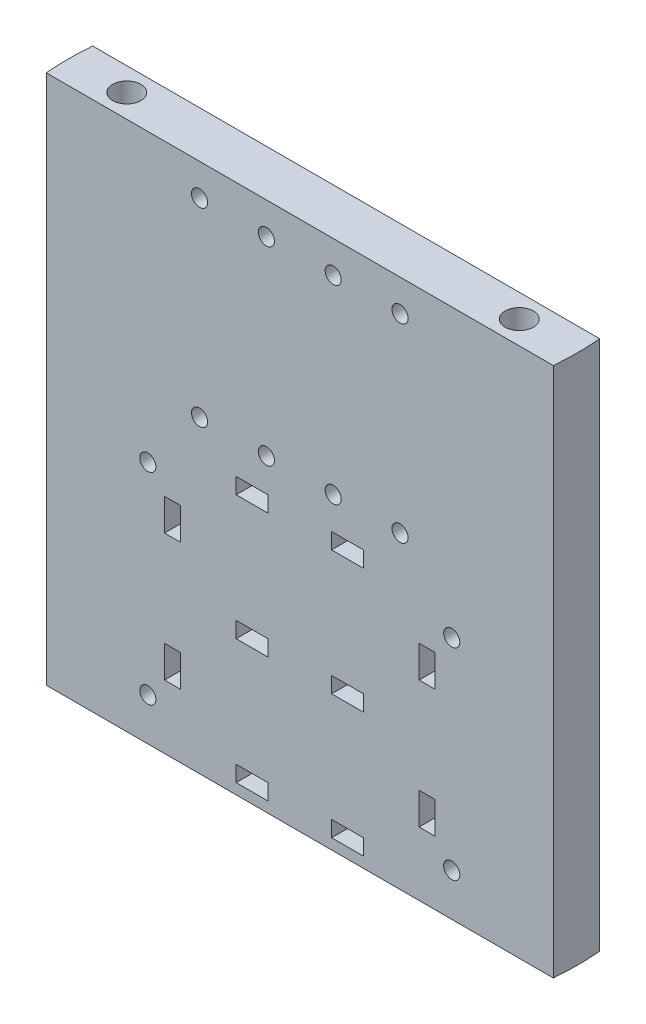
SolidWorks part; units mm, degrees
ref_plane "Front Plane" through (0, 0, 0) normal (0, 0, 1) x (1, 0, 0)
ref_plane "Top Plane" through (0, 0, 0) normal (0, 1, 0) x (1, 0, 0)
ref_plane "Right Plane" through (0, 0, 0) normal (1, 0, 0) x (0, 0, -1)
sketch "Sketch1" plane through (0, 0, 0) normal (0, 1, 0) x (1, 0, 0)
  line L0 (-60.706, 5.5591) -> (60.706, 5.5591)
  line L1 (-60.706, -5.5591) -> (60.706, -5.5591)
  arc A0 (60.706, -5.5591) -> (60.706, 5.5591) centre (0, 0) ccw
  arc A1 (-60.706, 5.5591) -> (-60.706, -5.5591) centre (0, 0) ccw
  point P1 (0, 5.5591)
  dimension "D1" = 121.92
  dimension "D4" = 60.96
  dimension "D2" = 121.412
  dimension "D3" = 121.412
  dimension "D5" = 5.5591
extrude "Boss-Extrude1" add sketch "Sketch1" along normal blind 127 contours L1 | L1 | L1 A0 L0 A1 region at (0, 0, 0)
sketch "Sketch2" plane through (0, 0, 0) normal (0, 1, 0) x (1, 0, 0)
  circle A0 centre (0, 0) radius 61.595
  dimension "D1" = 123.19
sketch "Sketch3" plane through (0, 0, 0) normal (0, 1, 0) x (1, 0, 0)
  circle A0 centre (0, 0) radius 63.5
  dimension "D1" = 127
ref_plane "Raft Top" through (0, 0, 9.9465) normal (0, 0, -1) x (-1, 0, 0)
sketch "Sketch10" plane through (0, 0, -5.5591) normal (0, 0, -1) x (-1, 0, 0)
  line L0 (-32.385, 2.54) -> (-32.385, 66.04)
  line L5 (-32.385, 66.04) -> (32.385, 66.04)
  line L10 (32.385, 66.04) -> (32.385, 2.54)
  line L11 (32.385, 2.54) -> (-32.385, 2.54)
  line L16 (60.706, 127) -> (60.706, 0) construction
  line L17 (61.595, 0) -> (-61.595, 0) construction
  line L18 (-60.706, 127) -> (-60.706, 0) construction
  dimension "D1" = 28.321
  dimension "D2" = 2.54
  dimension "D3" = 28.321
  dimension "D4" = 63.5
  dimension "D5" = 64.77
sketch "Sketch13" plane through (0, 127, 0) normal (0, 1, 0) x (1, 0, 0)
  line L2 (60.706, 5.5591) -> (-60.706, 5.5591)
  line L3 (-60.706, -5.5591) -> (60.706, -5.5591)
  line L4 (60.706, 5.5591) -> (-60.706, 5.5591)
  line L5 (-60.706, -5.5591) -> (60.706, -5.5591)
  line L6 (-46.99, 5.5591) -> (-46.99, -5.5591) construction
  line L7 (0, -55) -> (0, 55) construction
  line L8 (-32.385, 5.5591) -> (32.385, 5.5591) construction
  arc A2 (-60.706, 5.5591) -> (-60.706, -5.5591) centre (0, 0) ccw
  arc A3 (60.706, -5.5591) -> (60.706, 5.5591) centre (0, 0) ccw
  arc A4 (-60.706, 5.5591) -> (-60.706, -5.5591) centre (0, 0) ccw
  arc A5 (60.706, -5.5591) -> (60.706, 5.5591) centre (0, 0) ccw
  point P10 (-46.99, 0)
  point P13 (46.99, 0)
  dimension "D2" = 46.99
  dimension "D1" = 0
hole_wizard "Tap Drill for 1/4 Helicoil1" positions "Sketch14" profile "Sketch15" hole size "1/4-20" standard "ANSI Inch" end condition through all
sketch "Sketch14" plane through (0, 127, 0) normal (0, 1, 0) x (1, 0, 0)
  point P0 (-46.99, 0)
  point P3 (46.99, 0)
sketch "Sketch15" plane through (-46.99, 127, 0) normal (1, 0, 0) x (0, 0, 1)
  line L0 (0, 0) -> (0, 127)
  line L1 (0, 127) -> (3.3782, 127)
  line L2 (3.3782, 127) -> (3.3782, 0)
  line L5 (3.3782, 0) -> (0, 0)
  line L11 (0, -6.35) -> (0, 107.95) construction
  dimension "Thru Hole Dia." = 6.7564
  dimension "Thru Hole Depth" = 127
sketch "Sketch16" plane through (0, 0, 9.9465) normal (0, 0, -1) x (-1, 0, 0)
  line L0 (60.706, 127) -> (-60.706, 127) construction
  line L3 (0, 55) -> (0, -55) construction
  point P0 (-24.003, 119.38)
  point P1 (-8.001, 119.38)
  point P2 (-8.001, 73.914)
  point P3 (-24.003, 73.914)
  point P28 (8.001, 73.914)
  point P29 (24.003, 73.914)
  point P30 (8.001, 119.38)
  point P31 (24.003, 119.38)
  dimension "D1" = 16.002
  dimension "D2" = 45.466
  dimension "D3" = 8.001
  dimension "D4" = 7.62
sketch "Sketch19" plane through (0, 0, -5.5591) normal (0, 0, -1) x (-1, 0, 0)
  line L0 (0, 66.04) -> (0, 2.54) construction
  line L3 (-32.385, 34.29) -> (32.385, 34.29) construction
  line L8 (-15.24, 36.195) -> (-7.62, 36.195)
  line L9 (-15.24, 36.195) -> (-15.24, 32.385)
  line L10 (-15.24, 32.385) -> (-7.62, 32.385)
  line L11 (-7.62, 36.195) -> (-7.62, 32.385)
  line L19 (32.385, 45.72) -> (28.575, 45.72)
  line L20 (-15.24, 66.04) -> (-7.62, 66.04)
  line L21 (-15.24, 66.04) -> (-15.24, 62.23)
  line L22 (-15.24, 62.23) -> (-7.62, 62.23)
  line L23 (-7.62, 66.04) -> (-7.62, 62.23)
  line L36 (15.24, 62.23) -> (7.62, 62.23)
  line L37 (7.62, 66.04) -> (7.62, 62.23)
  line L38 (15.24, 66.04) -> (7.62, 66.04)
  line L39 (15.24, 66.04) -> (15.24, 62.23)
  line L40 (-15.24, 6.35) -> (-7.62, 6.35)
  line L41 (-7.62, 2.54) -> (-7.62, 6.35)
  line L42 (-15.24, 2.54) -> (-7.62, 2.54)
  line L43 (-15.24, 2.54) -> (-15.24, 6.35)
  line L44 (15.24, 2.54) -> (15.24, 6.35)
  line L45 (15.24, 2.54) -> (7.62, 2.54)
  line L46 (7.62, 2.54) -> (7.62, 6.35)
  line L47 (15.24, 6.35) -> (7.62, 6.35)
  line L48 (-32.385, 53.34) -> (-28.575, 53.34)
  line L49 (-32.385, 53.34) -> (-32.385, 45.72)
  line L50 (-32.385, 45.72) -> (-28.575, 45.72)
  line L51 (-28.575, 53.34) -> (-28.575, 45.72)
  line L52 (28.575, 53.34) -> (28.575, 45.72)
  line L53 (32.385, 53.34) -> (28.575, 53.34)
  line L54 (32.385, 53.34) -> (32.385, 45.72)
  line L55 (32.385, 15.24) -> (32.385, 22.86)
  line L56 (32.385, 15.24) -> (28.575, 15.24)
  line L57 (28.575, 15.24) -> (28.575, 22.86)
  line L58 (32.385, 22.86) -> (28.575, 22.86)
  line L59 (-32.385, 22.86) -> (-28.575, 22.86)
  line L60 (-28.575, 15.24) -> (-28.575, 22.86)
  line L61 (-32.385, 15.24) -> (-28.575, 15.24)
  line L62 (-32.385, 15.24) -> (-32.385, 22.86)
  line L63 (-32.385, 66.04) -> (32.385, 66.04) construction
  line L64 (32.385, 66.04) -> (32.385, 2.54) construction
  line L65 (32.385, 2.54) -> (-32.385, 2.54) construction
  line L66 (-32.385, 2.54) -> (-32.385, 66.04) construction
  line L67 (7.62, 36.195) -> (7.62, 32.385)
  line L68 (15.24, 32.385) -> (7.62, 32.385)
  line L69 (15.24, 36.195) -> (15.24, 32.385)
  line L70 (15.24, 36.195) -> (7.62, 36.195)
  point P10 (0, 34.29)
  point P12 (-15.24, 36.195)
  point P22 (-15.24, 66.04)
  point P41 (-32.385, 53.34)
  dimension "D1" = 7.62
  dimension "D2" = 3.81
  dimension "D3" = 15.24
  dimension "D4" = 1.905
  dimension "D5" = 15.24
  dimension "D6" = 7.62
  dimension "D7" = 3.81
  dimension "D8" = 19.05
  dimension "D9" = 3.81
  dimension "D10" = 7.62
hole_wizard "#8 Clearance Hole1" positions "Sketch20" profile "Sketch21" hole size "#8" standard "ANSI Inch" end condition through all
sketch "Sketch20" plane through (0, 0, -5.5591) normal (0, 0, -1) x (-1, 0, 0)
  point P3 (-8.001, 119.38)
  point P9 (-8.001, 73.914)
  point P12 (8.001, 73.914)
  point P21 (8.001, 119.38)
sketch "Sketch21" plane through (8.001, 119.38, -5.5591) normal (1, 0, 0) x (0, 1, 0)
  line L0 (0, 0) -> (0, 11.1181)
  line L1 (0, 11.1181) -> (1.9304, 11.1181)
  line L2 (1.9304, 11.1181) -> (1.9304, 0)
  line L5 (1.9304, 0) -> (0, 0)
  line L11 (0, -6.35) -> (0, 107.95) construction
  dimension "Thru Hole Dia." = 3.8608
  dimension "Thru Hole Depth" = 11.1181
extrude "Cut-Extrude3" cut sketch "Sketch19" against normal through all
hole_wizard "#8 Clearance Hole2" positions "Sketch22" profile "Sketch24" hole size "#8" standard "ANSI Inch" end condition through all
sketch "Sketch22" plane through (0, 0, -5.5591) normal (0, 0, -1) x (-1, 0, 0)
  point P0 (-24.003, 119.38)
  point P3 (-24.003, 73.914)
  point P6 (24.003, 73.914)
  point P9 (24.003, 119.38)
sketch "Sketch24" plane through (24.003, 119.38, -5.5591) normal (1, 0, 0) x (0, 1, 0)
  line L0 (0, 0) -> (0, 11.1181)
  line L1 (0, 11.1181) -> (1.9304, 11.1181)
  line L2 (1.9304, 11.1181) -> (1.9304, 0)
  line L5 (1.9304, 0) -> (0, 0)
  line L11 (0, -6.35) -> (0, 107.95) construction
  dimension "Thru Hole Dia." = 3.8608
  dimension "Thru Hole Depth" = 11.1181
sketch "Sketch29" plane through (0, 0, -5.5591) normal (0, 0, -1) x (-1, 0, 0)
  line L0 (60.706, 127) -> (60.706, 0) construction
  line L1 (-40.386, 66.04) -> (40.386, 66.04)
  line L2 (-40.386, 66.04) -> (-40.386, 2.54)
  line L3 (-40.386, 2.54) -> (40.386, 2.54)
  line L4 (40.386, 66.04) -> (40.386, 2.54)
  line L5 (-60.706, 127) -> (-60.706, 0) construction
  line L6 (61.595, 0) -> (-61.595, 0) construction
  line L7 (-40.386, 34.29) -> (40.386, 34.29) construction
  line L10 (32.385, 53.34) -> (40.386, 53.34) construction
  line L12 (32.385, 66.04) -> (32.385, 2.54) construction
  line L13 (0, 55) -> (0, -55) construction
  point P8 (36.3855, 58.42)
  point P20 (36.3855, 53.34)
  point P24 (36.3855, 10.16)
  point P28 (-36.3855, 58.42)
  point P30 (-36.3855, 10.16)
  dimension "D1" = 20.32
  dimension "D2" = 20.32
  dimension "D3" = 2.54
  dimension "D4" = 63.5
  dimension "D5" = 80.772
  dimension "D6" = 7.62
  dimension "D7" = 12.7
hole_wizard "#8 Clearance Hole3" positions "Sketch34" profile "Sketch35" hole size "#8" standard "ANSI Inch" end condition through all
sketch "Sketch34" plane through (0, 0, -5.5591) normal (0, 0, -1) x (-1, 0, 0)
  point P0 (-36.3855, 58.42)
  point P3 (-36.3855, 10.16)
  point P6 (36.3855, 10.16)
  point P9 (36.3855, 58.42)
sketch "Sketch35" plane through (36.3855, 58.42, -5.5591) normal (1, 0, 0) x (0, 1, 0)
  line L0 (0, 0) -> (0, 11.1181)
  line L1 (0, 11.1181) -> (1.9304, 11.1181)
  line L2 (1.9304, 11.1181) -> (1.9304, 0)
  line L5 (1.9304, 0) -> (0, 0)
  line L11 (0, -6.35) -> (0, 107.95) construction
  dimension "Thru Hole Dia." = 3.8608
  dimension "Thru Hole Depth" = 11.1181
extrude "Cut-Extrude4" cut sketch "Sketch10" against normal blind 5.08
